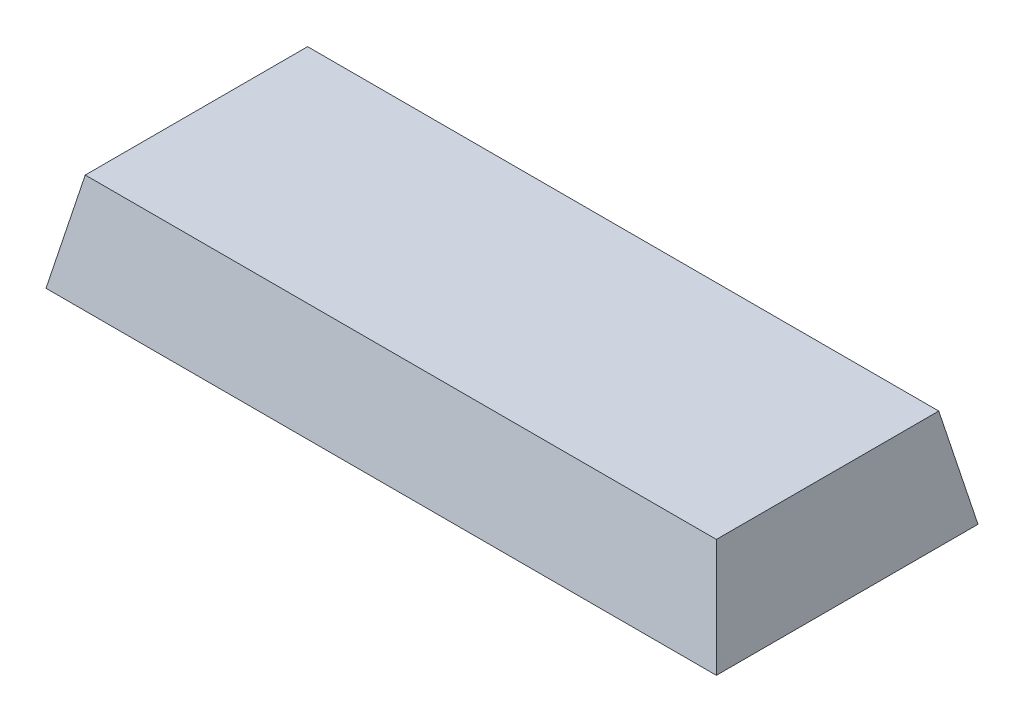
SolidWorks part; units mm, degrees
ref_plane "Front Plane" through (0, 0, 0) normal (0, 0, 1) x (1, 0, 0)
ref_plane "Top Plane" through (0, 0, 0) normal (0, 1, 0) x (1, 0, 0)
ref_plane "Right Plane" through (0, 0, 0) normal (1, 0, 0) x (0, 0, -1)
sketch "Sketch1" plane through (0, 0, 0) normal (0, 1, 0) x (1, 0, 0)
  line L1 (0, 0) -> (20.5, 0)
  line L2 (0, 0) -> (0, 8)
  line L3 (0, 8) -> (20.5, 8)
  line L4 (20.5, 0) -> (20.5, 8)
  dimension "D1" = 8
  dimension "D2" = 20.5
extrude "Boss-Extrude1" add sketch "Sketch1" along normal blind 3
sketch "Sketch2" plane through (0, 0, 0) normal (0, 0, 1) x (1, 0, 0)
  line L0 (0, 0) -> (0.6, 3)
  line L1 (0, 3) -> (20.5, 3) construction
  line L2 (0.6, 3) -> (0, 3)
  line L3 (0, 3) -> (0, 0)
  line L4 (20.5, 0) -> (19.9, 3)
  line L5 (19.9, 3) -> (20.5, 3)
  line L6 (20.5, 3) -> (20.5, 0)
  dimension "D1" = 0.6
  dimension "D2" = 0.6
extrude "Cut-Extrude1" cut sketch "Sketch2" against normal through all both and the other way through all
sketch "Sketch3" plane through (0, 0, 0) normal (1, 0, 0) x (0, 0, -1)
  line L0 (0, 0) -> (0.6, 3)
  line L1 (8, 3) -> (0, 3) construction
  line L2 (0.6, 3) -> (0, 3)
  line L3 (0, 3) -> (0, 0)
  line L4 (8, 3) -> (7.4, 3)
  line L5 (7.4, 3) -> (8, 0)
  line L6 (8, 3) -> (8, 0)
  dimension "D1" = 0.6
  dimension "D2" = 0.6
extrude "Cut-Extrude2" cut sketch "Sketch3" along normal through all both and the other way through all
sketch "Sketch4" plane through (0, 0, 0) normal (0, -1, 0) x (1, 0, 0)
  line L1 (10.25, 0) -> (10.25, -8) construction
  line L2 (20.5, -8) -> (0, -8) construction
  line L3 (0, 0) -> (20.5, 0) construction
  circle A0 centre (10.25, -3.75) radius 1.75
  dimension "D1" = 3.5
  dimension "D2" = 0
  dimension "D3" = 3.75
extrude "Cut-Extrude3" cut sketch "Sketch4" against normal blind 0.4
sketch "Sketch5" plane through (0, 0, 0) normal (0, -1, 0) x (1, 0, 0)
  line L5 (0, 0) -> (20.5, 0) construction
  line L6 (6.25, -8) -> (14.25, -8)
  line L7 (6.25, -8) -> (6.25, -6.8)
  line L8 (6.25, -6.8) -> (14.25, -6.8)
  line L9 (14.25, -8) -> (14.25, -6.8)
  point P2 (10.25, 0)
  dimension "D1" = 1.2
  dimension "D2" = 4
  dimension "D3" = 4
extrude "Boss-Extrude2" add sketch "Sketch5" along normal blind 2
fillet "Fillet1" radius 4 2 edges at (14.25, -2, -7.4) (6.25, -2, -7.4)
